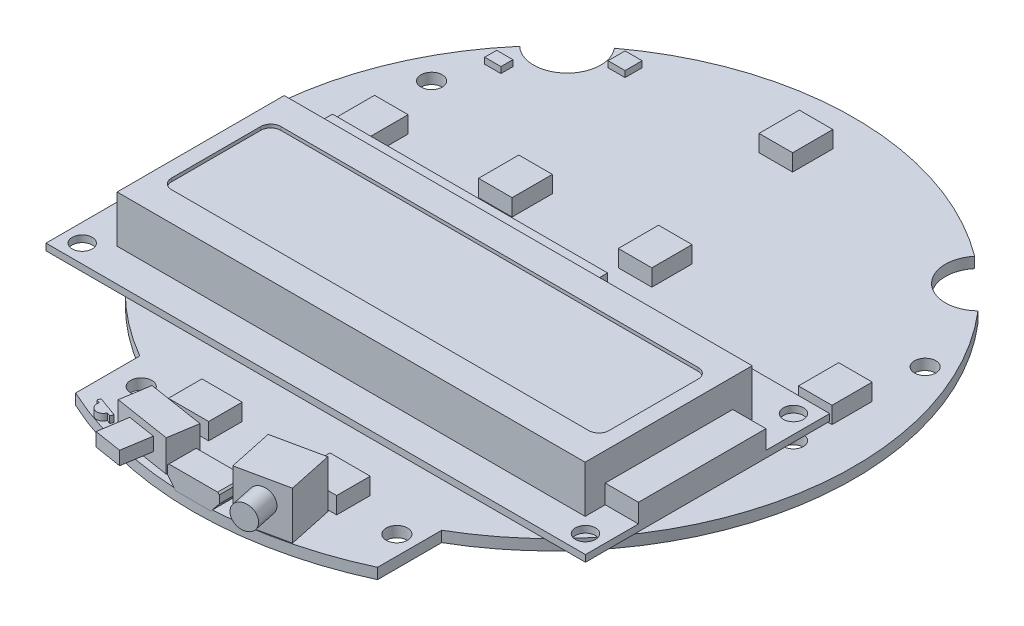
SolidWorks part; units mm, degrees
note: The reader was unsure of these and kept them because the rebuilt part matched: shared geometry of "LCD area<3>", "LCD area<4>", "LCD area<5>", "LCD area<6>", "PCB components<3>", "PCB components<5>", "PCB components<6>", "PCB components<7>", "PCB components<8>", "PCB components<9>".
material "Nickel"
ref_plane "Front Plane" through (0, 0, 0) normal (0, 0, 1) x (1, 0, 0)
ref_plane "Top Plane" through (0, 0, 0) normal (0, 1, 0) x (1, 0, 0)
ref_plane "Right Plane" through (0, 0, 0) normal (1, 0, 0) x (0, 0, -1)
sketch "PCB components" plane through (0, 0, 0) normal (0, 1, 0) x (1, 0, 0)
  line L0 (-36.1449, 9.6624) -> (-36.1449, 3.6624)
  line L1 (-12.4024, -44.8046) -> (-6.4024, -44.8046)
  line L2 (-6.4024, -44.8046) -> (-6.4024, -39.8046)
  line L3 (-6.4024, -39.8046) -> (-12.4024, -39.8046)
  line L4 (-12.4024, -39.8046) -> (-12.4024, -44.8046)
  line L5 (6.6936, -44.8188) -> (12.6936, -44.8188)
  line L6 (12.6936, -44.8188) -> (12.6936, -39.8188)
  line L7 (12.6936, -39.8188) -> (6.6936, -39.8188)
  line L8 (6.6936, -39.8188) -> (6.6936, -44.8188)
  line L9 (-16.5721, -49.7378) -> (-16.0083, -49.9431)
  line L10 (-16.0083, -49.9431) -> (-15.8373, -49.4732)
  line L11 (-15.8373, -49.4732) -> (-18.8443, -48.3787)
  line L12 (-18.8443, -48.3787) -> (-19.0153, -48.8486)
  line L13 (-19.0153, -48.8486) -> (-18.4515, -49.0538)
  line L14 (-36.1449, 3.6624) -> (-31.1449, 3.6624)
  line L15 (-31.1449, 3.6624) -> (-31.1449, 9.6624)
  line L16 (-31.1449, 9.6624) -> (-36.1449, 9.6624)
  line L17 (-17.6853, 6.7037) -> (-12.6853, 6.7037)
  line L18 (-12.6853, 6.7037) -> (-12.6853, 12.7037)
  line L19 (-12.6853, 12.7037) -> (-17.6853, 12.7037)
  line L20 (-17.6853, 12.7037) -> (-17.6853, 6.7037)
  line L21 (1.7861, 8.0557) -> (6.7861, 8.0557)
  line L22 (6.7861, 8.0557) -> (6.7861, 14.0557)
  line L23 (6.7861, 14.0557) -> (1.7861, 14.0557)
  line L24 (1.7861, 14.0557) -> (1.7861, 8.0557)
  line L25 (32.9551, 3.7374) -> (37.9551, 3.7374)
  line L26 (37.9551, 3.7374) -> (37.9551, 9.7374)
  line L27 (37.9551, 9.7374) -> (32.9551, 9.7374)
  line L28 (32.9551, 9.7374) -> (32.9551, 3.7374)
  line L29 (-2.5779, 33.4013) -> (2.4221, 33.4013)
  line L30 (2.4221, 33.4013) -> (2.4221, 39.4013)
  line L31 (2.4221, 39.4013) -> (-2.5779, 39.4013)
  line L32 (-2.5779, 39.4013) -> (-2.5779, 33.4013)
  line L33 (-24.7979, 33.1151) -> (-22.2579, 33.1151)
  line L34 (-22.2579, 33.1151) -> (-22.2579, 35.6551)
  line L35 (-22.2579, 35.6551) -> (-24.7979, 35.6551)
  line L36 (-24.7979, 35.6551) -> (-24.7979, 33.1151)
  line L37 (-34.442, 24.3803) -> (-32.029, 24.3803)
  line L38 (-32.029, 24.3803) -> (-32.029, 26.1583)
  line L39 (-32.029, 26.1583) -> (-34.442, 26.1583)
  line L40 (-34.442, 26.1583) -> (-34.442, 24.3803)
  line L41 (-13.7601, -50.9219) -> (-13.0718, -46.5761)
  line L42 (-13.0718, -46.5761) -> (-4.5777, -47.9214)
  line L43 (-4.5777, -47.9214) -> (-5.266, -52.2672)
  line L44 (-5.266, -52.2672) -> (-13.7601, -50.9219)
  line L45 (-11.7251, -51.2442) -> (-12.3942, -55.5931)
  line L46 (-12.3942, -55.5931) -> (-8.226, -56.2532)
  line L47 (-8.226, -56.2532) -> (-7.5377, -51.9074)
  line L48 (4.2888, -46.6348) -> (11.6249, -45.0754)
  line L49 (11.6249, -45.0754) -> (13.046, -51.7611)
  line L50 (13.046, -51.7611) -> (5.7099, -53.3204)
  line L51 (5.7099, -53.3204) -> (4.2888, -46.6348)
  arc A0 (-18.4515, -49.0538) -> (-16.5721, -49.7378) centre (-17.5118, -49.3958) ccw
sketch "PCB height map" plane through (0, 0, 0) normal (0, 0, 1) x (1, 0, 0)
  line L0 (0, 40.5) -> (0, 42.5) construction
  line L1 (-56, 0) -> (56, 0) construction
  line L3 (0, 40.5) -> (0, 34.5) construction
  line L4 (0, 34.5) -> (0, 33.5) construction
  line L5 (0, 33.5) -> (0, 31) construction
  line L6 (0, 31) -> (0, 29.4) construction
  line L7 (-56, 0) -> (-56, 2) construction
  line L8 (-45, 29.4) -> (45, 29.4)
  line L9 (-45, 29.4) -> (-45, 31)
  line L10 (-45, 31) -> (45, 31)
  line L11 (45, 29.4) -> (45, 31)
  line L12 (-40.55, 34.5) -> (39.85, 34.5)
  line L13 (-40.55, 34.5) -> (-40.55, 33.5)
  line L14 (-40.55, 33.5) -> (39.85, 33.5)
  line L15 (39.85, 34.5) -> (39.85, 33.5)
  line L16 (-34.85, 41.5) -> (34.9, 41.5)
  line L17 (-34.85, 41.5) -> (-34.85, 34.5)
  line L18 (-34.85, 34.5) -> (34.9, 34.5)
  line L19 (34.9, 41.5) -> (34.9, 34.5)
  line L20 (-33.75, 34.5) -> (7.25, 34.5)
  line L21 (-33.75, 34.5) -> (-33.75, 36.6)
  line L22 (-33.75, 36.6) -> (7.25, 36.6)
  line L23 (7.25, 34.5) -> (7.25, 36.6)
  line L24 (34.9, 37.3) -> (40.9, 37.3)
  line L25 (34.9, 37.3) -> (34.9, 34.5)
  line L26 (34.9, 34.5) -> (40.9, 34.5)
  line L27 (40.9, 37.3) -> (40.9, 34.5)
  line L28 (-56, 42.5) -> (56, 42.5) construction
  line L29 (-56, 42.5) -> (-56, 40.5) construction
  line L30 (-56, 40.5) -> (56, 40.5) construction
  line L31 (56, 42.5) -> (56, 40.5) construction
  line L32 (-56, 2) -> (56, 2) construction
  line L33 (56, 2) -> (56, 0) construction
  line L34 (-39.9884, 31) -> (-35.8497, 31) construction
  line L35 (-42.4014, 31.91) -> (-39.9884, 31.91)
  line L36 (-42.4014, 31.91) -> (-42.4014, 31)
  line L37 (-42.4014, 31) -> (-39.9884, 31)
  line L38 (-39.9884, 31.91) -> (-39.9884, 31)
  line L39 (-35.8497, 31.91) -> (-33.3097, 31.91)
  line L40 (-35.8497, 31.91) -> (-35.8497, 31)
  line L41 (-35.8497, 31) -> (-33.3097, 31)
  line L42 (-33.3097, 31.91) -> (-33.3097, 31)
  line L43 (-29.1709, 31) -> (-23.1709, 31)
  line L44 (-29.1709, 31) -> (-29.1709, 33.5)
  line L45 (-29.1709, 33.5) -> (-23.1709, 33.5)
  line L46 (-23.1709, 31) -> (-23.1709, 33.5)
  line L47 (-19.0321, 31) -> (-15.8321, 31)
  line L48 (-19.0321, 31) -> (-19.0321, 32)
  line L49 (-19.0321, 32) -> (-15.8321, 32)
  line L50 (-15.8321, 31) -> (-15.8321, 32)
  line L51 (-13.8521, 31) -> (-5.2521, 31)
  line L52 (-13.8521, 31) -> (-13.8521, 35.7)
  line L53 (-13.8521, 35.7) -> (-5.2521, 35.7)
  line L54 (-5.2521, 31) -> (-5.2521, 35.7)
  line L55 (-33.3097, 31) -> (-29.1709, 31) construction
  line L56 (-11.5521, 34.6) -> (-7.5521, 34.6)
  line L57 (-11.5521, 34.6) -> (-11.5521, 32.6)
  line L58 (-11.5521, 32.6) -> (-7.5521, 32.6)
  line L59 (-7.5521, 34.6) -> (-7.5521, 32.6)
  line L60 (-23.1709, 31) -> (-19.0321, 31) construction
  line L61 (-5.2521, 31) -> (6.2321, 31) construction
  line L62 (-15.8321, 31) -> (-13.8521, 31) construction
  line L63 (-2.625, 30.8) -> (2.625, 30.8)
  line L64 (2.625, 30.8) -> (3.8721, 32.3379)
  line L65 (3.8721, 32.3379) -> (3.8721, 33.5079)
  line L66 (3.8721, 33.5079) -> (3.63, 33.75)
  line L67 (3.63, 33.75) -> (-3.63, 33.75)
  line L68 (-3.63, 33.75) -> (-3.8721, 33.5079)
  line L69 (-3.8721, 33.5079) -> (-3.8721, 32.3379)
  line L70 (-3.8721, 32.3379) -> (-2.625, 30.8)
  line L72 (6.2321, 31) -> (13.7321, 31)
  line L73 (6.2321, 31) -> (6.2321, 38.1)
  line L74 (6.2321, 38.1) -> (13.7321, 38.1)
  line L75 (13.7321, 31) -> (13.7321, 38.1)
  line L76 (-18.4321, 32) -> (-18.4321, 31) construction
  line L77 (-16.4321, 32) -> (-16.4321, 31) construction
  line L78 (-18.4321, 32) -> (-16.4321, 32) construction
  circle A0 centre (9.9821, 35.06) radius 1.8
  point P0 (0, 41.5)
  point P93 (0, 0)
  point P95 (0, 0)
sketch "PCB area" plane through (0, 0, 0) normal (0, 1, 0) x (1, 0, 0)
  line L0 (-22.5, -48.5386) -> (-22.5, -38.9711)
  line L1 (22.5, -48.5386) -> (22.5, -38.9711)
  line L7 (-22.02, 35.88) -> (-22.02, 32.88)
  line L8 (-25.02, 35.88) -> (-22.02, 35.88)
  line L9 (-45, 0) -> (45, 0) construction
  line L10 (-40.55, 1.5) -> (-40.55, -34.9) construction
  line L11 (39.85, -34.9) -> (-40.55, -34.9) construction
  line L12 (39.85, 1.5) -> (39.85, -34.9) construction
  line L13 (39.85, 1.5) -> (-40.55, 1.5) construction
  line L14 (0, 0) -> (30.6899, 32.9109) construction
  line L15 (0, 0) -> (-30.6899, 32.9109) construction
  line L16 (0, -59.0145) -> (0, 51.1706) construction
  line L17 (-25.02, 35.88) -> (-25.02, 32.88)
  line L18 (-25.02, 32.88) -> (-22.02, 32.88)
  line L19 (-22.02, 35.88) -> (-22.02, 32.88)
  line L20 (-34.73, 26.77) -> (-31.73, 26.77)
  line L21 (-34.73, 26.77) -> (-34.73, 23.77)
  line L22 (-34.73, 23.77) -> (-31.73, 23.77)
  line L23 (-31.73, 26.77) -> (-31.73, 23.77)
  arc A4 (-22.5, -48.5386) -> (22.5, -48.5386) centre (0, 0) ccw
  circle A9 centre (-37.85, -1.2) radius 1.5
  circle A10 centre (37.15, -1.2) radius 1.5
  circle A13 centre (-15.1, 9.7) radius 2.5 construction
  circle A14 centre (-33.5814, 6.75) radius 2.5 construction
  circle A15 centre (4.359, 11.0556) radius 2.5 construction
  circle A16 centre (35.5323, 6.7) radius 2.5 construction
  circle A17 centre (-9.4664, -42.2776) radius 2.5 construction
  circle A18 centre (9.6779, -42.2776) radius 2.5 construction
  circle A19 centre (0, 36.4) radius 2.5 construction
  arc A20 (-26.8494, 36.1125) -> (-34.1516, 29.303) centre (-30.6899, 32.9109) cw
  arc A21 (34.1516, 29.303) -> (26.8494, 36.1125) centre (30.6899, 32.9109) cw
  arc A22 (-22.5, -38.9711) -> (-34.1516, 29.303) centre (0, 0) cw
  arc A24 (34.1516, 29.303) -> (22.5, -38.9711) centre (0, 0) cw
  arc A25 (-26.8494, 36.1125) -> (26.8494, 36.1125) centre (0, 0) cw
  circle A26 centre (37.15, -32.2) radius 1.5 construction
  circle A27 centre (-37.85, -32.2) radius 1.5 construction
  circle A29 centre (-18.44, -42.82) radius 1.59
  circle A30 centre (19.66, -42.82) radius 1.59
  circle A31 centre (-36.25, 18.27) radius 1.59
  circle A32 centre (37.44, 18.14) radius 1.59
  point P33 (0, -53.5)
extrude "Boss-Extrude PCB" add sketch "PCB area" along normal up to vertex (31 mm away) from vertex at 29.4 starting at point (0, 29.4, 0)
sketch "LCD area" plane through (0, 0, 0) normal (0, 1, 0) x (1, 0, 0)
  line L1 (-40.55, 1.5) -> (39.85, 1.5)
  line L2 (-40.55, 1.5) -> (-40.55, -34.9)
  line L4 (39.85, 1.5) -> (39.85, -34.9)
  line L5 (34.9, -30) -> (-34.85, -30)
  line L6 (34.9, -30) -> (34.9, -5.1)
  line L7 (34.9, -5.1) -> (-34.85, -5.1)
  line L8 (-34.85, -30) -> (-34.85, -5.1)
  line L9 (31.1, -25.65) -> (-31.1, -25.65)
  line L10 (32.6, -24.15) -> (32.6, -10.85)
  line L11 (31.1, -9.35) -> (-31.1, -9.35)
  line L12 (-32.6, -24.15) -> (-32.6, -10.85)
  line L13 (-33.75, 1) -> (7.25, 1)
  line L14 (0, -9.35) -> (0, -25.65) construction
  line L15 (-32.6, -17.5) -> (32.6, -17.5) construction
  line L16 (34.9, -8) -> (40.9, -8)
  line L17 (40.9, -8) -> (40.9, -27)
  line L18 (40.9, -27) -> (34.9, -27)
  line L19 (39.85, -34.9) -> (-40.55, -34.9)
  line L20 (-33.75, 1) -> (-33.75, -2.5)
  line L21 (-33.75, -2.5) -> (7.25, -2.5)
  line L22 (7.25, 1) -> (7.25, -2.5)
  arc A0 (31.1, -25.65) -> (32.6, -24.15) centre (31.1, -24.15) ccw
  arc A1 (-31.1, -25.65) -> (-32.6, -24.15) centre (-31.1, -24.15) cw
  arc A2 (32.6, -10.85) -> (31.1, -9.35) centre (31.1, -10.85) ccw
  arc A3 (-31.1, -9.35) -> (-32.6, -10.85) centre (-31.1, -10.85) ccw
  circle A4 centre (-37.85, -1.2) radius 1.5
  circle A5 centre (37.15, -1.2) radius 1.5
  circle A6 centre (37.15, -32.2) radius 1.5
  circle A7 centre (-37.85, -32.2) radius 1.5
  point P39 (32.6, -25.65)
  point P46 (-32.6, -9.35)
extrude "Boss-Extrude LCD PCB" add sketch "LCD area" along normal up to vertex (34.5 mm away) from vertex at 33.5 separate body starting at point (0, 33.5, 0)
extrude "Boss-Extrude LCD header" add sketch "LCD area<3>" against normal up to surface (5.6 mm away) from vertex at 36.6 contours L22 L13 L20 L21 up to face at (0, 31, 6.5802) starting at point (-33.75, 36.6, 0)
sketch "LCD area<3>" plane through (0, 0, 0) normal (0, 1, 0) x (1, 0, 0) same geometry as "LCD area"
extrude "Boss-Extrude LCD backlight" add sketch "LCD area<4>" along normal up to vertex (37.3 mm away) from vertex at 34.5 contours L18 L4 L16 L6 starting at point (40.9, 34.5, 0)
sketch "LCD area<4>" plane through (0, 0, 0) normal (0, 1, 0) x (1, 0, 0) same geometry as "LCD area"
extrude "Boss-Extrude LCD casing" add sketch "LCD area<5>" along normal up to vertex (41.5 mm away) from vertex at 34.5 contours L7 L8 L5 L6 starting at point (0, 34.5, 0)
sketch "LCD area<5>" plane through (0, 0, 0) normal (0, 1, 0) x (1, 0, 0) same geometry as "LCD area"
extrude "Cut-Extrude LCD screen" cut sketch "LCD area<6>" against normal blind 0.5 from surface at 41.5 contours L11 A3 L12 A1 L9 A0 L10 A2 starting at face at (0.025, 41.5, 17.55)
sketch "LCD area<6>" plane through (0, 0, 0) normal (0, 1, 0) x (1, 0, 0) same geometry as "LCD area"
extrude "Boss-Extrude LEDs" add sketch "PCB components<3>" along normal blind 2.5 from surface at 31 contours L1 L2 L3 L4 | L5 L6 L7 L8 | L15 L16 L0 L14 | L20 L17 L18 L19 | L24 L21 L22 L23 | L28 L25 L26 L27 | L32 L29 L30 L31 starting at face at (37.15, 31, 2.7)
sketch "PCB components<3>" plane through (0, 0, 0) normal (0, 1, 0) x (1, 0, 0) same geometry as "PCB components"
extrude "Boss-Extrude charging LED" add sketch "PCB components" along normal blind 1 from surface at 31 contours L13 A0 L9 L10 L11 L12 starting at face at (35.4551, 31, -6.7374)
extrude "Boss-Extrude light sensor" add sketch "PCB components<5>" along normal blind 0.91 from surface at 31 contours L39 L40 L37 L38 starting at face at (-0.0779, 31, -36.4013)
sketch "PCB components<5>" plane through (0, 0, 0) normal (0, 1, 0) x (1, 0, 0) same geometry as "PCB components"
extrude "Boss-Extrude temp sensor" add sketch "PCB components<6>" along normal blind 0.91 from surface at 31 contours L33 L34 L35 L36 starting at face at (-17.5118, 31, 49.3958)
sketch "PCB components<6>" plane through (0, 0, 0) normal (0, 1, 0) x (1, 0, 0) same geometry as "PCB components"
extrude "Boss-Extrude power switch base" add sketch "PCB components<7>" along normal blind 4.7 from surface at 31 contours L44 L43 L42 L41 starting at face at (-33.2355, 31, -25.2693)
sketch "PCB components<7>" plane through (0, 0, 0) normal (0, 1, 0) x (1, 0, 0) same geometry as "PCB components"
extrude "Boss-Extrude power switch" add sketch "PCB components<8>" along normal blind 2 from vertex at 32.6 separate body contours L46 L47 L44 L45 starting at point (-11.5521, 32.6, 0)
sketch "PCB components<8>" plane through (0, 0, 0) normal (0, 1, 0) x (1, 0, 0) same geometry as "PCB components"
extrude "Boss-Extrude USB connector" add sketch "PCB height map" against normal blind 4.06 from vertex at 53.5 starting at point (0, 0, 53.5)
extrude "Boss-Extrude button base" add sketch "PCB components<9>" along normal up to vertex (5.6 mm away) from vertex contours L51 L48 L49 L50
sketch "PCB components<9>" plane through (0, 0, 0) normal (0, 1, 0) x (1, 0, 0) same geometry as "PCB components"
sketch "Button circle" plane through (11.0905, 0, 52.1767) normal (0.2079, 0, 0.9781) x (0.9781, 0, -0.2079)
  line L0 (-4.1035, 31) -> (-5.5008, 31) construction
  line L1 (1.9992, 38.1) -> (-5.5008, 38.1) construction
  circle A0 centre (-1.7508, 35.06) radius 1.8
  point P11 (-1.7508, 38.1)
  dimension "D1" = 3.6
  dimension "D2" = 4.06
extrude "Boss-Extrude button" add sketch "Button circle" along normal blind 3.55 from surface at 0 starting at face at (8.9177, 33.84, 52.6386)
equation "\"D1@Boss-Extrude charging LED\" = \"Charging LED height@PCB height map@Enclosure master<1>.Part\""
equation "\"D1@Boss-Extrude LEDs\" = \"LED height@PCB height map@Enclosure master<1>.Part\""
equation "\"D1@Boss-Extrude light sensor\" = \"Light sensor height@PCB height map@Enclosure master<1>.Part\""
equation "\"D1@Boss-Extrude temp sensor\" = \"Temp sensor height@PCB height map@Enclosure master<1>.Part\""
equation "\"D1@Button circle\" = \"Button diameter@PCB height map@Enclosure master<1>.Part\""
equation "\"D1@Boss-Extrude power switch base\"=\"Power switch box height@PCB height map@Enclosure master-1.Part\""
equation "\"D1@Boss-Extrude power switch\"=\"Power switch height@PCB height map@Enclosure master-1.Part\""
equation "\"D2@Button circle\"=\"Button offset@PCB height map@Enclosure master-1.Part\""
